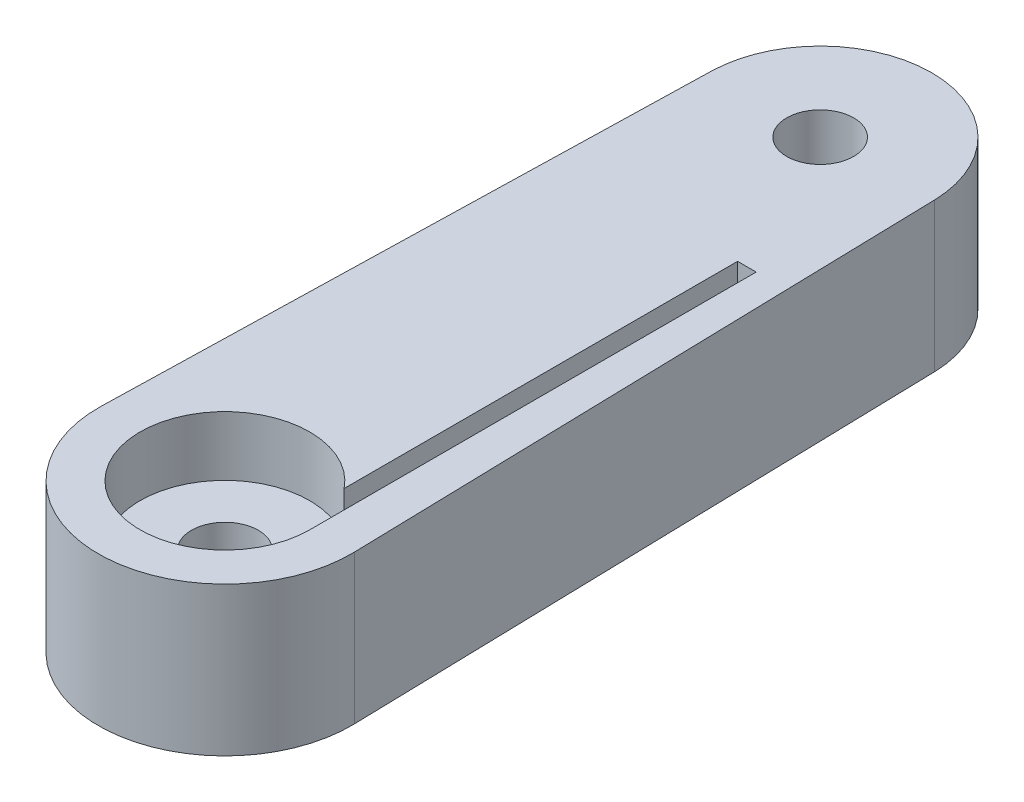
SolidWorks part; units mm, degrees
ref_plane "Front Plane" through (0, 0, 0) normal (0, 0, 1) x (1, 0, 0)
ref_plane "Top Plane" through (0, 0, 0) normal (0, 1, 0) x (1, 0, 0)
ref_plane "Right Plane" through (0, 0, 0) normal (1, 0, 0) x (0, 0, -1)
sketch "Sketch1" plane through (0, 0, 0) normal (0, 1, 0) x (1, 0, 0)
  line L0 (0, 0) -> (0, 20) construction
  line L1 (-4.2487, 0.1063) -> (-3.7488, 20.0938)
  line L2 (4.2487, 0.1063) -> (3.7488, 20.0938)
  circle A0 centre (0, 20) radius 3.75
  circle A1 centre (0, 0) radius 4.25
  circle A2 centre (0, 20) radius 1.125
  circle A3 centre (0, 0) radius 1.125
  dimension "D1" = 7.5
  dimension "D2" = 8.5
  dimension "D4" = 2.25
  dimension "D5" = 2.25
  dimension "D3" = 20
extrude "Boss-Extrude1" add sketch "Sketch1" along normal blind 5 contours L0 A1 L2 A0 | A1 L0 A0 L1 | A3 A1 | A0 A2 region at (2.8835, 0, -2.9565) region at (-2.1379, 0, -10.1229) region at (2.1379, 0, -10.1229) region at (-2.6087, 0, -17.4558)
sketch "Sketch2" plane through (0, 5, 0) normal (0, 1, 0) x (1, 0, 0)
  line L0 (2.85, 0) -> (2.85, 15)
  line L5 (2.225, 0) -> (2.225, 15)
  line L6 (2.225, 15) -> (2.85, 15)
  circle A0 centre (0, 0) radius 2.85
  dimension "D1" = 5.7
  dimension "D2" = 15
  dimension "D3" = 0.625
extrude "Cut-Extrude1" cut sketch "Sketch2" against normal blind 2
sketch "Sketch3" plane through (0, 0, 0) normal (0, -1, 0) x (1, 0, 0)
  line L0 (0, 0) -> (0, -20) construction
  line L7 (0, -10) -> (7.3913, -10) construction
  line L14 (2.125, -21.2269) -> (0, -22.4537)
  line L15 (0, 2.4537) -> (-2.125, 1.2269)
  line L16 (-2.125, 1.2269) -> (-2.125, -1.2269)
  line L17 (-2.125, -1.2269) -> (0, -2.4537)
  line L18 (0, -2.4537) -> (2.125, -1.2269)
  line L19 (2.125, -1.2269) -> (2.125, 1.2269)
  line L20 (2.125, 1.2269) -> (0, 2.4537)
  line L21 (2.125, -18.7731) -> (2.125, -21.2269)
  line L22 (0, -17.5463) -> (2.125, -18.7731)
  line L23 (-2.125, -18.7731) -> (0, -17.5463)
  line L24 (-2.125, -21.2269) -> (-2.125, -18.7731)
  line L25 (0, -22.4537) -> (-2.125, -21.2269)
  circle A1 centre (0, 0) radius 2.125 construction
  circle A4 centre (0, -20) radius 2.125 construction
  circle M6 centre (0, 0) radius 1.125
  dimension "D1" = 4.25
extrude "Cut-Extrude2" cut sketch "Sketch3" against normal blind 1.5 contours L19 L20 L15 L16 L17 L18 M6 region at (1.03, 0, 1.7841)
extrude "Cut-Extrude3" cut sketch "Sketch3<3>" against normal blind 2 contours L23 L22 L21 L14 L25 L24
sketch "Sketch3<3>" plane through (0, 0, 0) normal (0, -1, 0) x (1, 0, 0) same geometry as "Sketch3"
